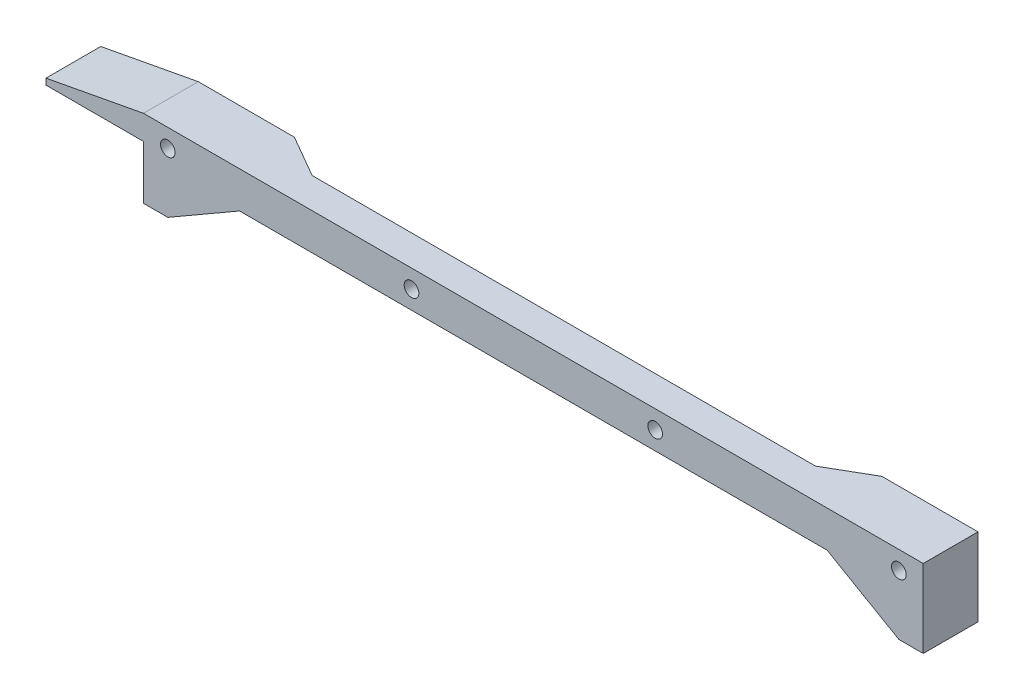
SolidWorks part; units mm, degrees
ref_plane "Front Plane" through (0, 0, 0) normal (0, 0, 1) x (1, 0, 0)
ref_plane "Top Plane" through (0, 0, 0) normal (0, 1, 0) x (1, 0, 0)
ref_plane "Right Plane" through (0, 0, 0) normal (1, 0, 0) x (0, 0, -1)
sketch "Sketch1" plane through (0, 0, 0) normal (0, 0, 1) x (1, 0, 0)
  line L0 (0, 12.7) -> (25.4, 12.7)
  line L5 (25.4, 12.7) -> (25.4, -1.27)
  line L6 (25.4, -1.27) -> (31.75, -1.27)
  line L7 (228.6, -1.27) -> (228.6, 19.05)
  line L12 (228.6, 19.05) -> (25.4, 19.05)
  line L13 (25.4, 19.05) -> (0, 14.2875)
  line L14 (0, 14.2875) -> (0, 12.7)
  line L15 (31.75, -1.27) -> (50.4475, 9.525)
  line L16 (50.4475, 9.525) -> (203.5525, 9.525)
  line L17 (203.5525, 9.525) -> (222.25, -1.27)
  line L18 (222.25, -1.27) -> (228.6, -1.27)
  point P2 (228.6, 20.2628)
  point P4 (228.6, 18.3693)
  point P7 (0, 0)
  point P9 (0, 0)
  point P10 (0, 0)
  point P11 (0, 15.0216)
  point P18 (50.8942, 12.7)
  point P20 (50.033, 12.7)
  dimension "D1" = 12.7
  dimension "D2" = 25.4
  dimension "D3" = 228.6
  dimension "D4" = 6.35
  dimension "D5" = 6.35
  dimension "D6" = 6.35
  dimension "D7" = 30
  dimension "D8" = 9.525
  dimension "D9" = 1.27
  dimension "D10" = 1.5875
extrude "Boss-Extrude1" add sketch "Sketch1" against normal up to surface (14.2752 mm away)
sketch "Sketch2" plane through (0, 0, 0) normal (0, 0, 1) x (1, 0, 0)
  line L0 (228.6, 19.05) -> (25.4, 19.05) construction
  line L1 (25.4, 12.7) -> (25.4, -1.27) construction
  line L2 (228.6, -1.27) -> (228.6, 19.05) construction
  circle A0 centre (31.75, 14.2875) radius 1.905
  circle A1 centre (95.25, 14.2875) radius 1.905
  circle A2 centre (158.75, 14.2875) radius 1.905
  circle A3 centre (222.25, 14.2875) radius 1.905
  point P7 (222.0806, 14.2875)
  dimension "D1" = 3.81
  dimension "D2" = 4.7625
  dimension "D3" = 6.35
  dimension "D5" = 6.35
  dimension "D4" = 4
extrude "Cut-Extrude2" cut sketch "Sketch2" against normal through all
sketch "Sketch3" plane through (0, 9.525, 0) normal (0, -1, 0) x (1, 0, 0)
  line L0 (50.4475, -14.2752) -> (61.4247, -7.9375)
  line L1 (61.4247, -7.9375) -> (192.5753, -7.9375)
  line L2 (192.5753, -7.9375) -> (203.5525, -14.2752)
  line L3 (203.5525, -14.2752) -> (50.4475, -14.2752)
  line L4 (50.4475, 0) -> (203.5525, 0) construction
  dimension "D1" = 7.9375
  dimension "D2" = 30
extrude "Cut-Extrude3" cut sketch "Sketch3" against normal through all
